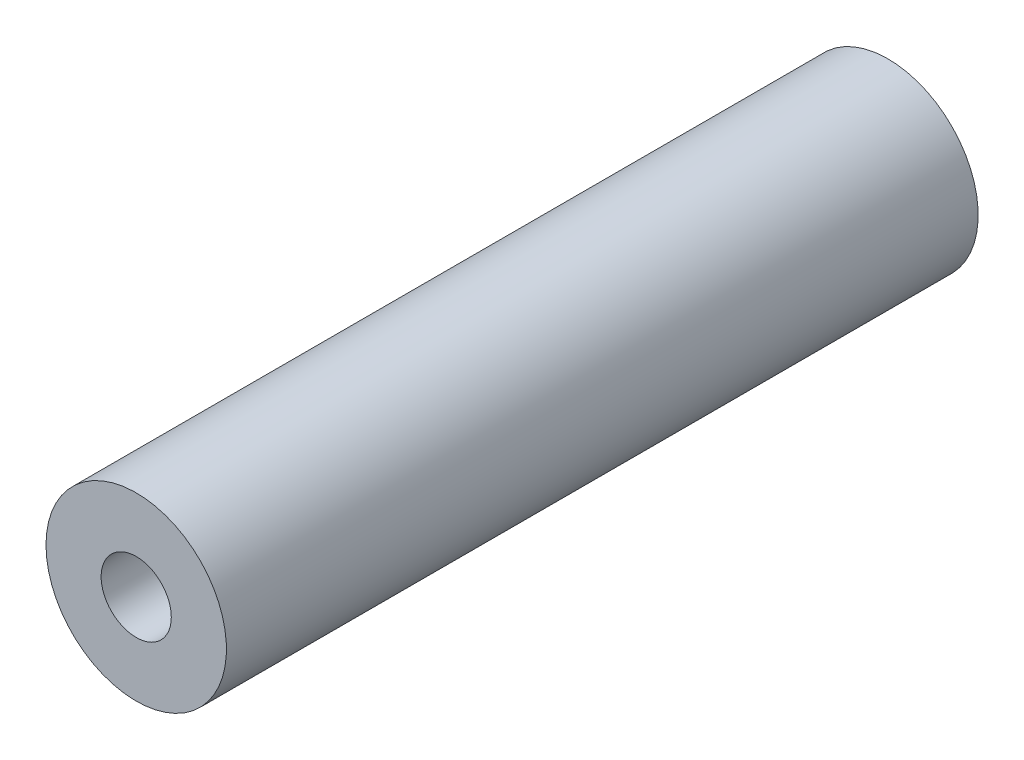
SolidWorks part; units mm, degrees
material "Liga 1060"
ref_plane "Plano frontal" through (0, 0, 0) normal (0, 0, 1) x (1, 0, 0)
ref_plane "Plano superior" through (0, 0, 0) normal (0, 1, 0) x (1, 0, 0)
ref_plane "Plano direito" through (0, 0, 0) normal (1, 0, 0) x (0, 0, -1)
sketch "Esboço1" plane through (0, 0, 0) normal (0, 0, 1) x (1, 0, 0)
  circle A0 centre (0, 0) radius 5.4
  dimension "D1" = 10.8
extrude "Ressalto-extrusão1" add sketch "Esboço1" along normal blind 45
hole_wizard "Furo roscado de M51" positions "3DSketch1" profile "Esboço2" tap size "M5" standard "ISO"
sketch3d "3DSketch1"
  line L0 (0, 0, 45) -> (0, 0, 0) construction
  point P0 (0, 0, 0)
  point P5 (0, 0, 45)
sketch "Esboço2" plane through (0, 0, 45) normal (1, 0, 0) x (0, -1, 0)
  line L0 (0, 0) -> (0, 15.2618)
  line L1 (0, 15.2618) -> (2.1, 14)
  line L2 (2.1, 14) -> (2.1, 0)
  line L5 (2.1, 0) -> (0, 0)
  line L10 (0, 15.2618) -> (-2.1, 14) construction
  line L11 (0, -6.35) -> (0, 107.95) construction
  dimension "Tap Drill Dia." = 4.2
  dimension "Tap Drill Depth" = 14
  dimension "Drill Angle" = 118
cosmetic thread "Rosca de furo2"
sketch "Esboço3" plane through (0, 0, 0) normal (0, 0, -1) x (-1, 0, 0)
  line L0 (-3, 0) -> (3, 0) construction
  circle A0 centre (0, 0) radius 3 construction
  point P3 (0, 3)
  point P9 (0, 0)
  point P10 (0, 0)
  point P11 (0, 0)
  dimension "D1" = 6
hole_wizard "Furo roscado de M21" positions "3DSketch2" profile "Esboço6" tap size "M2" standard "ISO"
sketch3d "3DSketch2"
  point P0 (0, 3, 0)
sketch "Esboço6" plane through (0, 3, 0) normal (1, 0, 0) x (0, 1, 0)
  line L0 (0, 0) -> (0, 8.4807)
  line L1 (0, 8.4807) -> (0.8, 8)
  line L2 (0.8, 8) -> (0.8, 0)
  line L5 (0.8, 0) -> (0, 0)
  line L10 (0, 8.4807) -> (-0.8, 8) construction
  line L11 (0, -6.35) -> (0, 107.95) construction
  dimension "Tap Drill Dia." = 1.6
  dimension "Tap Drill Depth" = 8
  dimension "Drill Angle" = 118
cosmetic thread "Rosca de furo3"
pattern_circular "PadrãoCircular1" count 3 over 360 about axis through (0, 0, 0) along (0, 0, 1) of "Furo roscado de M21"
cosmetic thread "Rosca de furo4"
cosmetic thread "Rosca de furo5"
